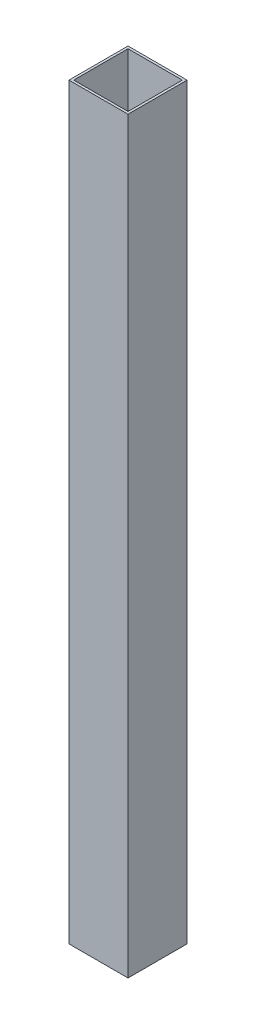
SolidWorks part; units mm, degrees
material "6061 Alloy"
ref_plane "Front Plane" through (0, 0, 0) normal (0, 0, 1) x (1, 0, 0)
ref_plane "Top Plane" through (0, 0, 0) normal (0, 1, 0) x (1, 0, 0)
ref_plane "Right Plane" through (0, 0, 0) normal (1, 0, 0) x (0, 0, -1)
sketch "Sketch1" plane through (0, 0, 0) normal (0, 1, 0) x (1, 0, 0)
  line L1 (19.05, 19.05) -> (-19.05, 19.05)
  line L2 (19.05, 19.05) -> (19.05, -19.05)
  line L3 (19.05, -19.05) -> (-19.05, -19.05)
  line L4 (-19.05, 19.05) -> (-19.05, -19.05)
  line L5 (19.05, 19.05) -> (-19.05, -19.05) construction
  line L6 (19.05, -19.05) -> (-19.05, 19.05) construction
  point P0 (0, 0)
  dimension "D1" = 38.1
extrude "Extrude-Thin1" add sketch "Sketch1" along normal blind 482.6 thin thin type one direction reverse wall 1.524
